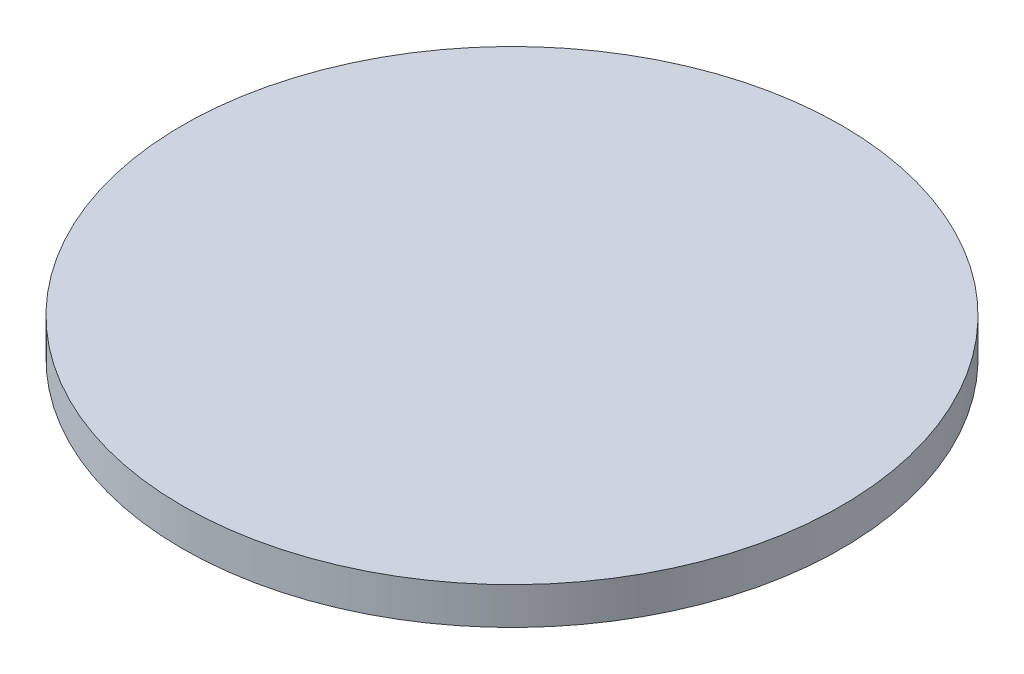
SolidWorks part; units mm, degrees
material "6061-T6 (SS)"
ref_plane "Front Plane" through (0, 0, 0) normal (0, 0, 1) x (1, 0, 0)
ref_plane "Top Plane" through (0, 0, 0) normal (0, 1, 0) x (1, 0, 0)
ref_plane "Right Plane" through (0, 0, 0) normal (1, 0, 0) x (0, 0, -1)
sketch "Sketch1" plane through (0, 0, 0) normal (0, 1, 0) x (1, 0, 0)
  circle A0 centre (0, 0) radius 85.725
  dimension "D1" = 171.45
extrude "Boss-Extrude1" add sketch "Sketch1" along normal mid plane 9.652
sketch "Sketch2" plane through (0, -4.826, 0) normal (0, -1, 0) x (1, 0, 0)
  circle A0 centre (0, 0) radius 19.05
  dimension "D1" = 38.1
extrude "Cut-Extrude1" [suppressed] cut sketch "Sketch2" against normal up to surface (9.652 mm away) up to face at (0, 4.826, 85.725)
ref_plane "Plane1" through (-85.725, 0, 0) normal (-1, 0, 0) x (0, 0, 1)
sketch "Sketch3" plane through (-85.725, 0, 0) normal (-1, 0, 0) x (0, 0, 1)
  circle A0 centre (0, 0) radius 1.6637
  dimension "D1" = 3.3274
extrude "Cut-Extrude2" [suppressed] cut sketch "Sketch3" against normal blind 15.24
pattern_circular "CirPattern1" [suppressed] count 3 over 360 of bodies 105
